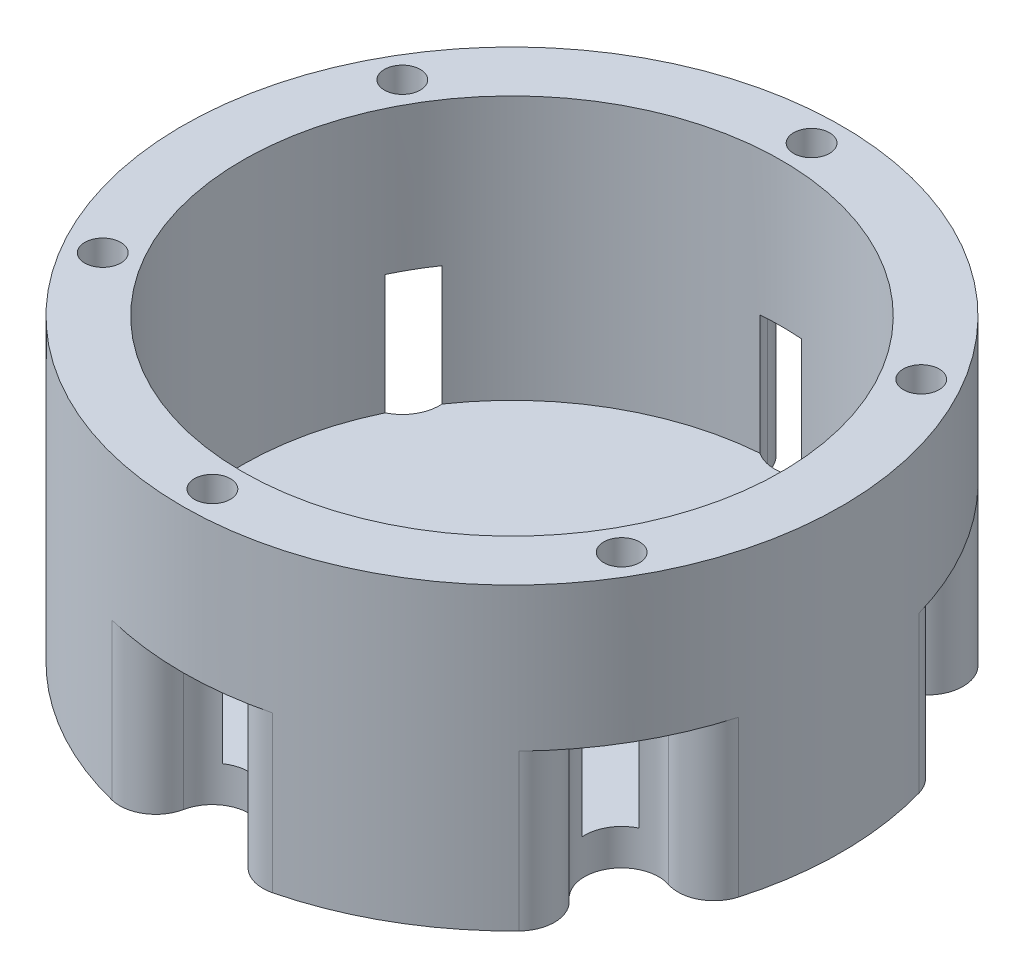
SolidWorks part; units mm, degrees
ref_plane "Front Plane" through (0, 0, 0) normal (0, 0, 1) x (1, 0, 0)
ref_plane "Top Plane" through (0, 0, 0) normal (0, 1, 0) x (1, 0, 0)
ref_plane "Right Plane" through (0, 0, 0) normal (1, 0, 0) x (0, 0, -1)
sketch "Sketch1" plane through (0, 0, 0) normal (0, 1, 0) x (1, 0, 0)
  circle A0 centre (0, 0) radius 27.5
  circle A1 centre (0, 0) radius 25 construction
  circle A2 centre (0, 25) radius 1.5
  circle A3 centre (21.6506, 12.5) radius 1.5
  circle A4 centre (21.6506, -12.5) radius 1.5
  circle A5 centre (0, -25) radius 1.5
  circle A6 centre (-21.6506, -12.5) radius 1.5
  circle A7 centre (-21.6506, 12.5) radius 1.5
  point P19 (0, 0)
  point P31 (0, 0)
  dimension "D1" = 55
  dimension "D2" = 50
  dimension "D3" = 3
  dimension "D4" = 6
extrude "Boss-Extrude1" add sketch "Sketch1" along normal blind 25
sketch "Sketch2" plane through (0, 25, 0) normal (0, 1, 0) x (1, 0, 0)
  circle A0 centre (0, 0) radius 22.5
  dimension "D1" = 45
extrude "Cut-Extrude1" cut sketch "Sketch2" against normal blind 22
sketch "Sketch3" plane through (0, 0, 0) normal (0, -1, 0) x (1, 0, 0)
  circle A0 centre (0, 25) radius 3.1
  dimension "D1" = 6.2
extrude "Cut-Extrude2" cut sketch "Sketch3" against normal blind 13
fillet "Fillet1" radius 3 2 edges at (-1.9213, 6.5, 27.4328) (1.9213, 6.5, 27.4328)
pattern_circular "CirPattern1" count 6 over 360 about axis through (0, 25, 0) along (0, -1, 0) of "Cut-Extrude2", "Fillet1" reverse direction yes
